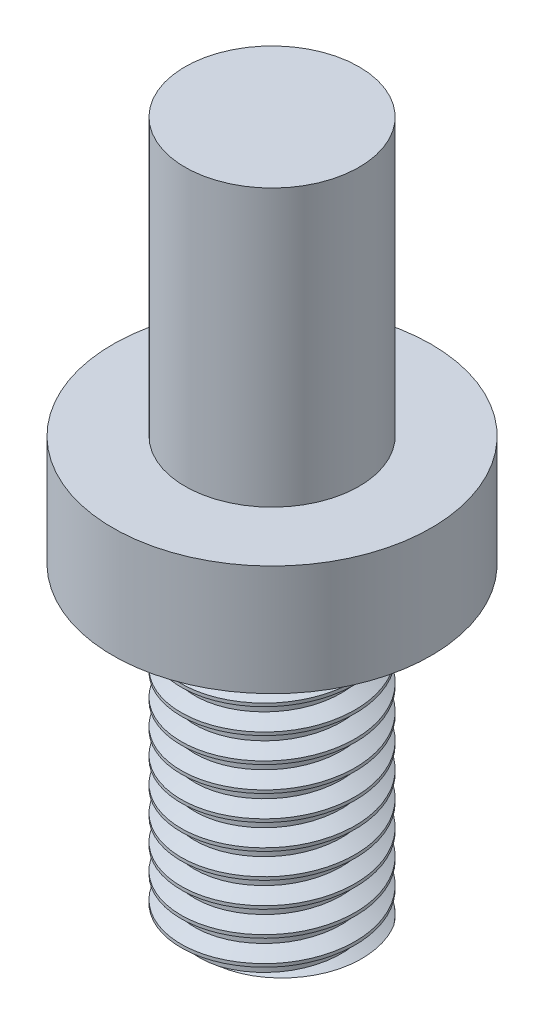
SolidWorks part; units mm, degrees
ref_plane "Front Plane" through (0, 0, 0) normal (0, 0, 1) x (1, 0, 0)
ref_plane "Top Plane" through (0, 0, 0) normal (0, 1, 0) x (1, 0, 0)
ref_plane "Right Plane" through (0, 0, 0) normal (1, 0, 0) x (0, 0, -1)
sketch "Sketch1" plane through (0, 0, 0) normal (0, 0, 1) x (1, 0, 0)
  line L0 (0, -12.5) -> (0, 12.5)
  line L1 (0, -12.5) -> (3.15, -12.5)
  line L2 (3.15, -12.5) -> (3.15, -1.5)
  line L3 (3.15, -1.5) -> (5.7593, -1.5)
  line L4 (5.7593, -1.5) -> (5.7593, 2.5)
  line L5 (5.7593, 2.5) -> (3.15, 2.5)
  line L6 (3.15, 2.5) -> (3.15, 12.5)
  line L7 (3.15, 12.5) -> (0, 12.5)
  point P4 (0, 0)
  dimension "D1" = 25
  dimension "D2" = 3.15
  dimension "D3" = 11
  dimension "D4" = 4
revolve "Revolve1" add sketch "Sketch1" angle 360 about L0
thread "Thread1" pitch 0.9071 method cut trim with start face yes trim with end face yes profile "Thread Profile1" start angle 0, offset 1, length 0, pitch 0.9071, diameter 6.3
ref_plane "Plane1" through (3.15, -13.5, 0) normal (0, 0, 1) x (1, 0, 0)
sketch "Thread Profile1" plane through (3.15, -13.5, 0) normal (0, 0, 1) x (1, 0, 0)
  line L0 (0, 0) -> (0, 0.9071) construction
  line L11 (0, 0) -> (0, 0.7937)
  line L12 (0, 0.7937) -> (-0.491, 0.5103)
  line L13 (-0.491, 0.5103) -> (-0.491, 0.2835)
  line L15 (-0.491, 0.2835) -> (0, 0)
  line L17 (-0.491, 0.3969) -> (0, 0.3969) construction
  point P2 (0, 0)
  dimension "Pitch" = 0.9071
  dimension "Profile_Angle" = 60
  dimension "Profile_Land" = 0.2268
  dimension "Profile_Height" = 0.491
